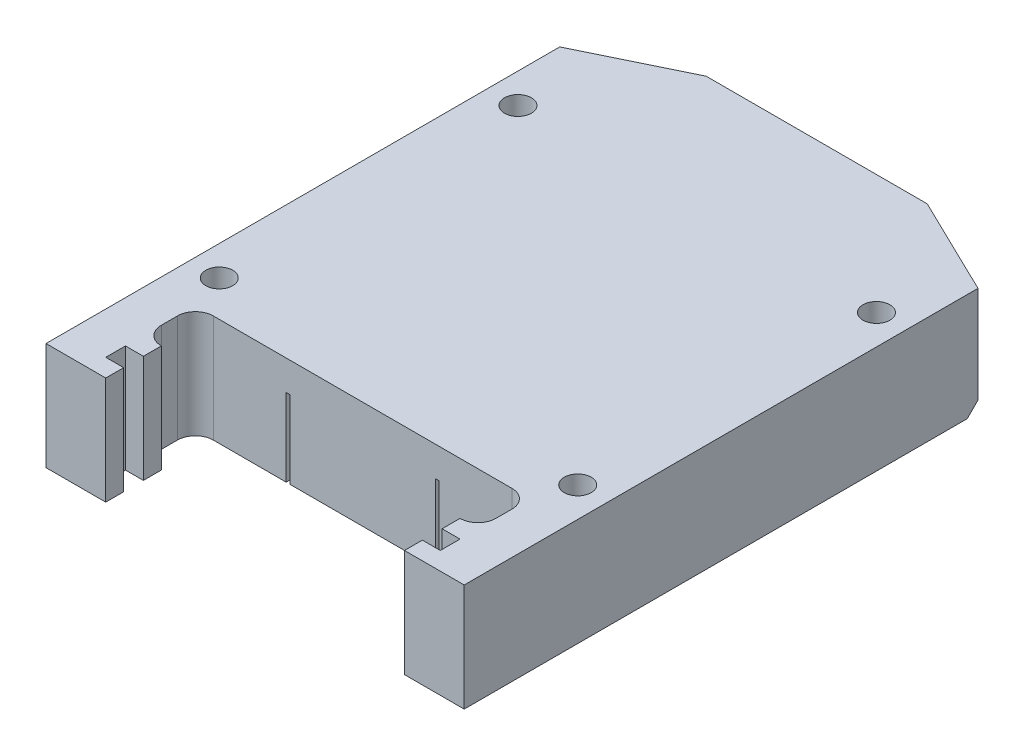
SolidWorks part; units mm, degrees
ref_plane "前视基准面" through (0, 0, 0) normal (0, 0, 1) x (1, 0, 0)
ref_plane "上视基准面" through (0, 0, 0) normal (0, 1, 0) x (1, 0, 0)
ref_plane "右视基准面" through (0, 0, 0) normal (1, 0, 0) x (0, 0, -1)
sketch "草图1" plane through (0, 0, 0) normal (0, 0, 1) x (1, 0, 0)
  line L1 (0, 0) -> (70, 0)
  line L2 (0, 0) -> (0, 18)
  line L3 (0, 18) -> (70, 18)
  line L4 (70, 0) -> (70, 18)
  dimension "D1" = 70
  dimension "D2" = 18
extrude "凸台-拉伸1" add sketch "草图1" along normal blind 60
sketch "草图2" plane through (0, 0, 60) normal (0, 0, 1) x (1, 0, 0)
  line L0 (13.4, 0) -> (13.4, 5)
  line L1 (0, 0) -> (70, 0) construction
  line L2 (13.4, 5) -> (9.4, 5)
  line L3 (35, 18) -> (35, 0) construction
  line L4 (70, 18) -> (0, 18) construction
  line L5 (9.4, 5) -> (9.4, 12)
  line L6 (9.4, 12) -> (60.6, 12)
  line L7 (13.4, 0) -> (56.6, 0)
  line L8 (60.6, 5) -> (60.6, 12)
  line L9 (56.6, 5) -> (60.6, 5)
  line L10 (56.6, 0) -> (56.6, 5)
  point P11 (35, 12)
  dimension "D1" = 25.6
  dimension "D2" = 12
  dimension "D3" = 5
  dimension "D4" = 4
extrude "切除-拉伸1" cut sketch "草图2" against normal through all
sketch "草图3" plane through (13.4, 0, 0) normal (1, 0, 0) x (0, 0, -1)
  line L0 (0, 0) -> (-60, 0) construction
  line L1 (0, 5) -> (-15, 5)
  line L2 (0, 5) -> (0, 0)
  line L3 (0, 0) -> (-15, 0)
  line L4 (-15, 5) -> (-15, 0)
  line L5 (-60, 5) -> (-60, 0) construction
  dimension "D1" = 45
extrude "切除-拉伸2" cut sketch "草图3" against normal blind 1
sketch "草图4" plane through (56.6, 0, 0) normal (-1, 0, 0) x (0, 0, 1)
  line L0 (0, 5) -> (60, 5) construction
  line L1 (0, 0) -> (15, 0)
  line L2 (0, 0) -> (0, 5)
  line L3 (0, 5) -> (15, 5)
  line L4 (15, 0) -> (15, 5)
  line L5 (60, 0) -> (60, 5) construction
  dimension "D1" = 45
extrude "切除-拉伸3" cut sketch "草图4" against normal blind 1
sketch "草图5" plane through (0, 5, 0) normal (0, 1, 0) x (1, 0, 0)
  line L0 (57.6, -15) -> (57.6, 0) construction
  line L1 (60.6, 0) -> (57.6, 0)
  line L2 (60.6, 0) -> (60.6, -11)
  line L3 (60.6, -11) -> (57.6, -11)
  line L4 (57.6, 0) -> (57.6, -11)
  line L5 (57.6, -15) -> (56.6, -15) construction
  dimension "D1" = 4
extrude "切除-拉伸4" cut sketch "草图5" against normal blind 1
sketch "草图6" plane through (0, 5, 0) normal (0, 1, 0) x (1, 0, 0)
  line L0 (12.4, 0) -> (12.4, -15) construction
  line L1 (9.4, 0) -> (12.4, 0)
  line L2 (9.4, 0) -> (9.4, -11)
  line L3 (9.4, -11) -> (12.4, -11)
  line L4 (12.4, 0) -> (12.4, -11)
  line L5 (12.4, -15) -> (13.4, -15) construction
  dimension "D1" = 4
extrude "切除-拉伸5" cut sketch "草图6" against normal blind 1
chamfer "倒角1" distance 1 angle 45 4 edges at (59.1, 4, 11) (10.9, 4, 11) (12.4, 2.5, 15) (57.6, 2.5, 15)
sketch "草图21" plane through (0, 18, 0) normal (0, 1, 0) x (1, 0, 0)
  line L0 (0, 0) -> (16.5, 8)
  line L1 (16.5, 8) -> (53.5, 8)
  line L2 (53.5, 8) -> (70, 0)
  line L3 (0, -60) -> (0, 0) construction
  line L4 (70, 0) -> (0, 0) construction
  line L5 (0, 0) -> (70, 0)
  dimension "D1" = 37
  dimension "D2" = 16.5
  dimension "D3" = 8
extrude "凸台-拉伸9" add sketch "草图21" against normal blind 6
sketch "草图7" plane through (0, 12, 0) normal (0, -1, 0) x (1, 0, 0)
  line L0 (60.6, 60) -> (9.4, 60) construction
  line L1 (20.25, -4) -> (49.75, -4)
  line L2 (20.25, -4) -> (20.25, 5)
  line L3 (20.25, 5) -> (49.75, 5)
  line L4 (49.75, -4) -> (49.75, 5)
  line L5 (35, 60) -> (35, -8) construction
  line L6 (53.5, -8) -> (16.5, -8) construction
  dimension "D1" = 29.5
  dimension "D2" = 9
  dimension "D3" = 55
  dimension "D4" = 14.75
extrude "切除-拉伸7" cut sketch "草图7" against normal blind 4
sketch "草图9" plane through (0, 12, 0) normal (0, -1, 0) x (1, 0, 0)
  line L0 (60.6, 60) -> (9.4, 60) construction
  line L1 (16.5, 60) -> (53.5, 60)
  line L2 (16.5, 60) -> (16.5, 52.5)
  line L3 (16.5, 52.5) -> (53.5, 52.5)
  line L4 (53.5, 60) -> (53.5, 52.5)
  line L5 (35, 60) -> (35, -8) construction
  line L7 (53.5, -8) -> (16.5, -8) construction
  dimension "D1" = 37
  dimension "D2" = 7.5
extrude "凸台-拉伸3" add sketch "草图9" along normal blind 12
sketch "草图10" plane through (0, 0, 60) normal (0, 0, 1) x (1, 0, 0)
  line L1 (0, 0) -> (70, 0)
  line L2 (0, 0) -> (0, 18)
  line L3 (0, 18) -> (70, 18)
  line L4 (70, 0) -> (70, 18)
extrude "凸台-拉伸4" add sketch "草图10" along normal blind 8
chamfer "倒角4" distance 4 angle 45 1 edges at (35, 16, 5)
sketch "草图11" plane through (0, 0, 0) normal (0, -1, 0) x (1, 0, 0)
  line L0 (16.5, 52.5) -> (53.5, 52.5) construction
  line L1 (31, 52.5) -> (39, 52.5)
  line L2 (31, 52.5) -> (31, 63.5)
  line L3 (31, 63.5) -> (39, 63.5)
  line L4 (39, 52.5) -> (39, 63.5)
  line L5 (35, 68) -> (35, 52.5) construction
  line L6 (0, 68) -> (70, 68) construction
  dimension "D1" = 8
  dimension "D2" = 11
  dimension "D3" = 4
extrude "切除-拉伸8" cut sketch "草图11" against normal blind 3
sketch "草图12" plane through (0, 0, 0) normal (0, -1, 0) x (1, 0, 0)
  line L0 (16.5, 52.5) -> (31, 52.5) construction
  line L1 (22.2, 34.5) -> (22.8, 34.5)
  line L2 (22.2, 34.5) -> (22.2, 68)
  line L3 (22.2, 68) -> (22.8, 68)
  line L4 (22.8, 34.5) -> (22.8, 68)
  line L5 (0, 68) -> (70, 68) construction
  line L6 (39, 52.5) -> (53.5, 52.5) construction
  line L7 (47.2, 34.5) -> (47.8, 34.5)
  line L8 (47.2, 34.5) -> (47.2, 68)
  line L9 (47.2, 68) -> (47.8, 68)
  line L10 (47.8, 34.5) -> (47.8, 68)
  line L11 (35, 68) -> (35, 52.5) construction
  line L12 (16.5, 52.5) -> (53.5, 52.5) construction
  dimension "D1" = 0.6
  dimension "D2" = 0.6
  dimension "D3" = 24.4
  dimension "D4" = 12.2
  dimension "D5" = 18
  dimension "D6" = 18
extrude "切除-拉伸9" cut sketch "草图12" against normal blind 13
sketch "草图13" plane through (0, 12, 0) normal (0, -1, 0) x (1, 0, 0)
  line L1 (17.1, 0) -> (16.5, 0)
  line L2 (17.1, 0) -> (17.1, 52.5)
  line L3 (17.1, 52.5) -> (16.5, 52.5)
  line L4 (16.5, 0) -> (16.5, 52.5)
  line L5 (53.5, 52.5) -> (52.9, 52.5)
  line L6 (53.5, 52.5) -> (53.5, 0)
  line L7 (53.5, 0) -> (52.9, 0)
  line L8 (52.9, 52.5) -> (52.9, 0)
  dimension "D1" = 0.6
  dimension "D2" = 0.6
  dimension "D3" = 52.5
  dimension "D4" = 52.5
extrude "凸台-拉伸5" add sketch "草图13" along normal blind 7
sketch "草图14" plane through (0, 5, 0) normal (0, -1, 0) x (1, 0, 0)
  line L0 (17.1, 0) -> (17.1, 52.5) construction
  line L1 (16.5, 0) -> (17.1, 0)
  line L2 (16.5, 0) -> (16.5, 10)
  line L3 (16.5, 10) -> (17.1, 10)
  line L4 (17.1, 0) -> (17.1, 10)
  line L5 (52.9, 52.5) -> (52.9, 0) construction
  line L6 (53.5, 0) -> (52.9, 0)
  line L7 (53.5, 0) -> (53.5, 10)
  line L8 (53.5, 10) -> (52.9, 10)
  line L9 (52.9, 0) -> (52.9, 10)
  line L10 (9.4, 10) -> (12.4, 10) construction
  line L11 (57.6, 10) -> (60.6, 10) construction
extrude "凸台-拉伸6" add sketch "草图14" along normal blind 1
sketch "草图15" plane through (0, 5, 0) normal (0, -1, 0) x (1, 0, 0)
  line L0 (17.1, 10) -> (17.1, 52.5) construction
  line L1 (17.1, 11) -> (9.4, 11)
  line L2 (17.1, 11) -> (17.1, 60)
  line L3 (17.1, 60) -> (9.4, 60)
  line L4 (9.4, 11) -> (9.4, 60)
  line L5 (52.9, 11) -> (60.6, 11)
  line L6 (52.9, 11) -> (52.9, 60)
  line L7 (52.9, 60) -> (60.6, 60)
  line L8 (60.6, 11) -> (60.6, 60)
  line L9 (9.4, 11) -> (12.4, 11) construction
  line L10 (52.9, 52.5) -> (52.9, 10) construction
  line L11 (57.6, 11) -> (60.6, 11) construction
extrude "凸台-拉伸7" add sketch "草图15" along normal blind 0.6
sketch "草图18" plane through (0, 4, 0) normal (0, -1, 0) x (1, 0, 0)
  line L0 (9.4, 11) -> (9.4, 10) construction
  line L1 (17.1, 0) -> (9.4, 0)
  line L2 (17.1, 0) -> (17.1, 10)
  line L3 (17.1, 10) -> (9.4, 10)
  line L4 (9.4, 0) -> (9.4, 10)
  line L5 (9.4, 10) -> (12.4, 10) construction
  line L6 (57.6, 10) -> (60.6, 10) construction
  line L7 (52.9, 0) -> (60.6, 0)
  line L8 (52.9, 0) -> (52.9, 10)
  line L9 (52.9, 10) -> (60.6, 10)
  line L10 (60.6, 0) -> (60.6, 10)
extrude "凸台-拉伸8" add sketch "草图18" along normal blind 0.6
chamfer "倒角5" distance 1.8 angle 45 4 edges at (63.8, 0, 0) (35, 12, -8)
sketch "草图22" plane through (0, 0, 0) normal (0, -1, 0) x (1, 0, 0)
  line L0 (22.8, 52.5) -> (22.8, 68) construction
  line L1 (22.8, 57.5) -> (25.8, 57.5)
  line L2 (22.8, 57.5) -> (22.8, 64)
  line L3 (22.8, 64) -> (25.8, 64)
  line L4 (25.8, 57.5) -> (25.8, 64)
  line L5 (47.2, 68) -> (47.2, 52.5) construction
  line L6 (47.2, 57.5) -> (44.2, 57.5)
  line L7 (47.2, 57.5) -> (47.2, 64)
  line L8 (47.2, 64) -> (44.2, 64)
  line L9 (44.2, 57.5) -> (44.2, 64)
  line L10 (22.8, 52.5) -> (31, 52.5) construction
  line L11 (39, 52.5) -> (47.2, 52.5) construction
  dimension "D1" = 6.5
  dimension "D2" = 6.5
  dimension "D3" = 3
  dimension "D4" = 3
  dimension "D5" = 5
  dimension "D6" = 5
extrude "切除-拉伸10" cut sketch "草图22" against normal blind 1
sketch "草图23" plane through (0, 18, 0) normal (0, 1, 0) x (1, 0, 0)
  line L0 (0, -68) -> (0, -86)
  line L1 (0, -86) -> (10, -86)
  line L2 (10, -86) -> (10, -83)
  line L3 (10, -83) -> (7, -83)
  line L4 (7, -83) -> (7, -79.7)
  line L5 (7, -79.7) -> (10, -79.7)
  line L6 (10, -79.7) -> (10, -76.7)
  line L7 (10, -76.7) -> (7, -76.7)
  line L8 (7, -76.7) -> (7, -68)
  line L9 (70, -68) -> (0, -68) construction
  line L10 (35, 8) -> (35, -68) construction
  line L11 (53.5, 8) -> (16.5, 8) construction
  line L12 (63, -68) -> (70, -68)
  line L13 (63, -76.7) -> (63, -68)
  line L14 (60, -76.7) -> (63, -76.7)
  line L15 (60, -79.7) -> (60, -76.7)
  line L16 (63, -79.7) -> (60, -79.7)
  line L17 (63, -83) -> (63, -79.7)
  line L18 (60, -83) -> (63, -83)
  line L19 (60, -86) -> (60, -83)
  line L20 (70, -86) -> (60, -86)
  line L21 (7, -68) -> (0, -68)
  line L22 (70, -68) -> (70, -86)
  dimension "D1" = 10
  dimension "D2" = 18
  dimension "D3" = 3
  dimension "D4" = 3
  dimension "D5" = 3
  dimension "D6" = 3.3
extrude "凸台-拉伸10" add sketch "草图23" against normal blind 18
fillet "圆角1" radius 3 4 edges at (7, 9, 76.7) (63, 9, 68) (63, 9, 76.7)
hole_wizard "打孔尺寸(%根据十字)槽半沉头木螺钉的类型2" positions "草图27" profile "草图26" countersink size "M4" standard "GB" end condition through all
sketch "草图27" plane through (0, 0, 0) normal (0, -1, 0) x (-1, 0, 0)
  line L0 (-70, -86) -> (-70, -1.8) construction
  line L1 (-70, 0) -> (-57.6, 0) construction
  point P0 (-65, -12)
  point P2 (-65, -62)
  point P4 (-5, -12)
  point P6 (-5, -62)
  dimension "D1" = 50
  dimension "D2" = 60
  dimension "D3" = 5
  dimension "D4" = 12
sketch "草图26" plane through (65, 0, 12) normal (1, 0, 0) x (0, 0, -1)
  line L0 (0, 0) -> (0, 18)
  line L1 (0, 18) -> (2.25, 18)
  line L2 (2.25, 18) -> (2.25, 2.05)
  line L3 (2.25, 2.05) -> (4.3, 0)
  line L5 (4.3, 0) -> (0, 0)
  line L6 (-2.25, 2.05) -> (-4.3, 0) construction
  line L11 (0, -6.35) -> (0, 107.95) construction
  dimension "通孔孔直径" = 4.5
  dimension "通孔孔深度" = 18
  dimension "近端锥形沉头孔直径" = 8.6
  dimension "近端锥形沉头孔角度" = 90
